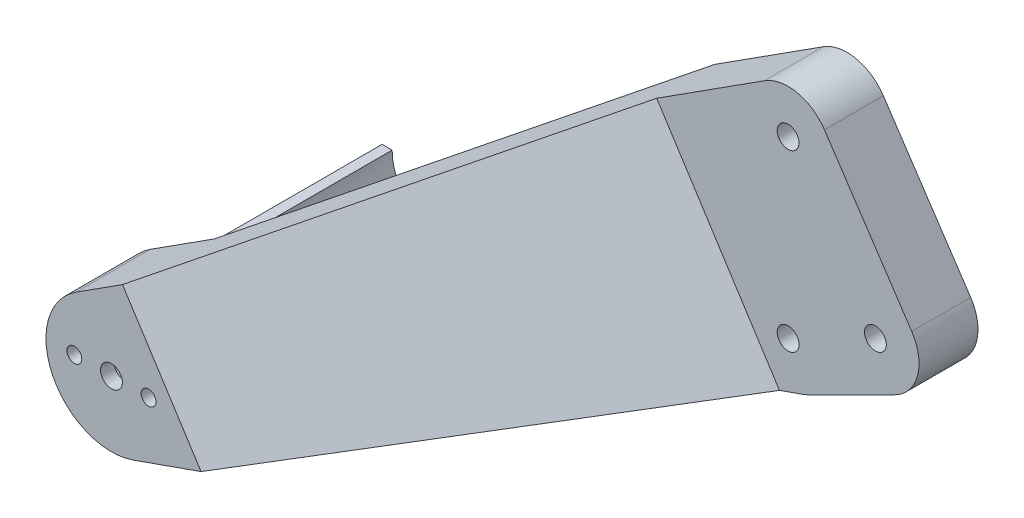
SolidWorks part; units mm, degrees
ref_plane "Front Plane" through (0, 0, 0) normal (0, 0, 1) x (1, 0, 0)
ref_plane "Top Plane" through (0, 0, 0) normal (0, 1, 0) x (1, 0, 0)
ref_plane "Right Plane" through (0, 0, 0) normal (1, 0, 0) x (0, 0, -1)
sketch "Sketch1" plane through (0, 0, 0) normal (0, 0, 1) x (1, 0, 0)
  line L1 (3.3289, -9.4297) -> (-95.0067, -44.1445)
  line L2 (-108.0914, -17.3695) -> (-5.3942, 48.4203)
  line L3 (8.3205, 45.547) -> (28.3205, 15.547)
  line L4 (24.4721, 1.0557) -> (4.4721, -8.9443)
  arc A0 (4.4721, -8.9443) -> (3.3289, -9.4297) centre (0, 0) cw
  arc A1 (-95.0067, -44.1445) -> (-108.0914, -17.3695) centre (-100, -30) cw
  arc A2 (-5.3942, 48.4203) -> (8.3205, 45.547) centre (0, 40) cw
  arc A3 (28.3205, 15.547) -> (24.4721, 1.0557) centre (20, 10) cw
  dimension "D1" = 15
  dimension "D5" = 10
  dimension "D8" = 10
  dimension "D9" = 10
  dimension "D2" = 30
  dimension "D3" = 40
  dimension "D4" = 100
  dimension "D6" = 20
  dimension "D7" = 30
extrude "Boss-Extrude1" add sketch "Sketch1" along normal blind 17
sketch "Sketch2" plane through (0, 0, 17) normal (0, 0, 1) x (1, 0, 0)
  circle A0 centre (-100, -30) radius 2.5
  circle A1 centre (0, 0) radius 2.5
  circle A2 centre (0, 40) radius 2.5
  circle A3 centre (20, 10) radius 2.5
  arc A4 (24.4721, 1.0557) -> (28.3205, 15.547) centre (20, 10) ccw construction
  dimension "D1" = 5
  dimension "D2" = 5
extrude "Cut-Extrude1" cut sketch "Sketch2" against normal through all
sketch "Sketch3" plane through (0, 0, 17) normal (0, 0, 1) x (1, 0, 0)
  line L0 (-108.5, -30) -> (-91.5, -30) construction
  circle A0 centre (-108.5, -30) radius 1.7
  circle A1 centre (-91.5, -30) radius 1.7
  circle A3 centre (-100, -30) radius 2.5 construction
  point P4 (-100, -30)
  dimension "D1" = 3.4
  dimension "D2" = 17
extrude "Cut-Extrude2" cut sketch "Sketch3" against normal through all
sketch "Sketch7" plane through (0, 0, 0) normal (0, 0, -1) x (-1, 0, 0)
  circle A0 centre (100, -30) radius 12.7
  dimension "D1" = 25.4
extrude "Cut-Extrude6" cut sketch "Sketch7" against normal blind 13
sketch "Sketch6" plane through (0, 0, 17) normal (0, 0, 1) x (1, 0, 0)
  circle A0 centre (-100, -30) radius 12.7
  dimension "D1" = 25.4
extrude "Cut-Extrude5" [suppressed] cut sketch "Sketch6" against normal blind 13
sketch "Sketch4" [suppressed] plane through (0, 0, 13) normal (0, 0, -1) x (-1, 0, 0)
  circle A0 centre (100, -30) radius 5.5
  dimension "D1" = 11
extrude "Cut-Extrude3" cut sketch "Sketch4" against normal blind 0.9
sketch "Sketch5" [suppressed] plane through (0, 0, 4) normal (0, 0, 1) x (1, 0, 0)
  circle A0 centre (-100, -30) radius 5.5
  dimension "D1" = 11
extrude "Cut-Extrude4" [suppressed] cut sketch "Sketch5" against normal blind 0.9
sketch "Sketch8" plane through (0, 0, 0) normal (0, 0, -1) x (-1, 0, 0)
  line L0 (112.7, -30) -> (115, -30)
  line L2 (87.0096, -37.5) -> (89.0015, -36.35)
  line L4 (-8.3205, 45.547) -> (-28.3205, 15.547)
  line L5 (-24.4721, 1.0557) -> (-4.4721, -8.9443)
  line L6 (-3.3289, -9.4297) -> (95.0067, -44.1445)
  line L7 (108.0914, -17.3695) -> (5.3942, 48.4203)
  circle A0 centre (100, -30) radius 12.7 construction
  circle A1 centre (100, -30) radius 12.7 construction
  arc A2 (89.0015, -36.35) -> (112.7, -30) centre (100, -30) ccw
  arc A4 (5.3942, 48.4203) -> (-8.3205, 45.547) centre (0, 40) ccw
  arc A5 (-28.3205, 15.547) -> (-24.4721, 1.0557) centre (-20, 10) ccw
  arc A6 (-4.4721, -8.9443) -> (-3.3289, -9.4297) centre (0, 0) ccw
  arc A7 (95.0067, -44.1445) -> (108.0914, -17.3695) centre (100, -30) ccw
  arc A11 (87.0096, -37.5) -> (115, -30) centre (100, -30) ccw
  dimension "D2" = 150
  dimension "D1" = 0
extrude "Boss-Extrude2" add sketch "Sketch8" along normal blind 60
sketch "Sketch9" [suppressed] plane through (0, 0, 17) normal (0, 0, 1) x (1, 0, 0)
  line L0 (-90.2712, -38.1634) -> (-88.5093, -39.6418)
  line L1 (-112.7, -30) -> (-115, -30)
  circle A0 centre (-100, -30) radius 12.7 construction
  arc A1 (-112.7, -30) -> (-90.2712, -38.1634) centre (-100, -30) ccw
  arc A3 (-115, -30) -> (-88.5093, -39.6418) centre (-100, -30) ccw
  dimension "D1" = 15
  dimension "D2" = 140
extrude "Boss-Extrude3" [suppressed] add sketch "Sketch9" along normal blind 60
sketch "Sketch10" plane through (0, 0, 0) normal (0, 0, -1) x (-1, 0, 0)
  line L0 (-3.3289, -9.4297) -> (74.8434, -37.0264)
  line L1 (95.0067, -44.1445) -> (-3.3289, -9.4297) construction
  line L2 (74.8434, -37.0264) -> (93.4462, -7.9875)
  line L6 (112.7, -30) -> (115, -30)
  line L7 (108.0914, -17.3695) -> (5.3942, 48.4203)
  line L8 (-8.3205, 45.547) -> (-28.3205, 15.547)
  line L9 (-24.4721, 1.0557) -> (-4.4721, -8.9443)
  line L10 (-3.3289, -9.4297) -> (95.0067, -44.1445)
  line L11 (87.0096, -37.5) -> (89.0015, -36.35)
  line L19 (93.4462, -7.9875) -> (5.3942, 48.4203)
  line L20 (-8.3205, 45.547) -> (-28.3205, 15.547)
  line L21 (-24.4721, 1.0557) -> (-4.4721, -8.9443)
  arc A6 (115, -30) -> (108.0914, -17.3695) centre (100, -30) ccw
  arc A7 (5.3942, 48.4203) -> (-8.3205, 45.547) centre (0, 40) ccw
  arc A8 (-28.3205, 15.547) -> (-24.4721, 1.0557) centre (-20, 10) ccw
  arc A10 (-4.4721, -8.9443) -> (-3.3289, -9.4297) centre (0, 0) ccw
  arc A11 (87.0096, -37.5) -> (95.0067, -44.1445) centre (100, -30) ccw
  arc A18 (112.7, -30) -> (89.0015, -36.35) centre (100, -30) ccw
  arc A20 (5.3942, 48.4203) -> (-8.3205, 45.547) centre (0, 40) ccw
  arc A21 (-28.3205, 15.547) -> (-24.4721, 1.0557) centre (-20, 10) ccw
  arc A22 (-4.4721, -8.9443) -> (-3.3289, -9.4297) centre (0, 0) ccw
  dimension "D2" = 115
  dimension "D1" = 0
extrude "Boss-Extrude4" add sketch "Sketch10" along normal blind 51.5
sketch "Sketch12" plane through (0, 0, 17) normal (0, 0, 1) x (1, 0, 0)
  circle A0 centre (0, 0) radius 2.5 construction
  circle A1 centre (20, 10) radius 2.5 construction
  circle A2 centre (0, 40) radius 2.5 construction
  circle A3 centre (0, 0) radius 2.5
  circle A4 centre (20, 10) radius 2.5
  circle A5 centre (0, 40) radius 2.5
extrude "Cut-Extrude7" cut sketch "Sketch12" against normal through all
sketch "Sketch13" plane through (-23.5628, 36.7812, 0) normal (-0.5394, 0.842, 0) x (0.842, 0.5394, 0)
  line L0 (32.2333, -17) -> (-87.7667, -17)
  line L1 (21.577, -17) -> (-100.3861, -17) construction
  line L2 (-87.7667, -17) -> (-7.7667, 38)
  line L3 (-7.7667, 38) -> (32.2333, 38)
  line L4 (32.2333, -17) -> (32.2333, 51.5) construction
  line L7 (32.2333, 38) -> (33.2333, 38)
  line L9 (32.2333, -17) -> (33.2333, -17)
  line L10 (33.2333, 38) -> (33.2333, -17)
  dimension "D1" = 55
  dimension "D2" = 120
  dimension "D3" = 40
  dimension "D4" = 1
extrude "Cut-Extrude8" cut sketch "Sketch13" against normal through all
sketch "Sketch14" plane through (-23.5628, 36.7812, 0) normal (-0.5394, 0.842, 0) x (0.842, 0.5394, 0)
  line L0 (-82.9936, 0) -> (-7.9936, 51.5)
  line L1 (-82.9936, 51.5) -> (21.577, 51.5) construction
  line L2 (-7.9936, 51.5) -> (-82.9936, 51.5)
  line L3 (-82.9936, 51.5) -> (-82.9936, 0)
  dimension "D1" = 75
extrude "Cut-Extrude9" cut sketch "Sketch14" against normal through all
sketch "Sketch15" [suppressed] plane through (0, 0, 17) normal (0, 0, 1) x (1, 0, 0)
  line L0 (-93.4462, -7.9875) -> (-74.8434, -37.0264)
  line L6 (-90.2712, -38.1634) -> (-88.5093, -39.6418)
  line L7 (-95.0067, -44.1445) -> (3.3289, -9.4297)
  line L8 (4.4721, -8.9443) -> (24.4721, 1.0557)
  line L9 (28.3205, 15.547) -> (8.3205, 45.547)
  line L10 (-5.3942, 48.4203) -> (-108.0914, -17.3695)
  line L11 (-115, -30) -> (-112.7, -30)
  line L13 (-74.8434, -37.0264) -> (3.3289, -9.4297)
  line L14 (4.4721, -8.9443) -> (24.4721, 1.0557)
  line L15 (28.3205, 15.547) -> (8.3205, 45.547)
  line L16 (-5.3942, 48.4203) -> (-93.4462, -7.9875)
  arc A6 (-95.0067, -44.1445) -> (-88.5093, -39.6418) centre (-100, -30) ccw
  arc A7 (3.3289, -9.4297) -> (4.4721, -8.9443) centre (0, 0) ccw
  arc A8 (24.4721, 1.0557) -> (28.3205, 15.547) centre (20, 10) ccw
  arc A9 (8.3205, 45.547) -> (-5.3942, 48.4203) centre (0, 40) ccw
  arc A10 (-108.0914, -17.3695) -> (-115, -30) centre (-100, -30) ccw
  arc A11 (-90.2712, -38.1634) -> (-112.7, -30) centre (-100, -30) ccw
  arc A13 (3.3289, -9.4297) -> (4.4721, -8.9443) centre (0, 0) ccw
  arc A14 (24.4721, 1.0557) -> (28.3205, 15.547) centre (20, 10) ccw
  arc A15 (8.3205, 45.547) -> (-5.3942, 48.4203) centre (0, 40) ccw
  dimension "D2" = 115
  dimension "D1" = 0
extrude "Boss-Extrude5" [suppressed] add sketch "Sketch15" along normal blind 51.5
sketch "Sketch16" [suppressed] plane through (0, 0, 0) normal (0, 0, -1) x (-1, 0, 0)
  circle A0 centre (0, 0) radius 2.5 construction
  circle A1 centre (-20, 10) radius 2.5 construction
  circle A2 centre (0, 40) radius 2.5 construction
  circle A3 centre (0, 0) radius 2.5
  circle A4 centre (-20, 10) radius 2.5
  circle A5 centre (0, 40) radius 2.5
extrude "Cut-Extrude10" [suppressed] cut sketch "Sketch16" against normal through all
sketch "Sketch17" [suppressed] plane through (-23.5628, 36.7812, 0) normal (-0.5394, 0.842, 0) x (0.842, 0.5394, 0)
  line L0 (32.2333, 0) -> (-87.7667, 0)
  line L1 (21.577, 0) -> (-100.3861, 0) construction
  line L2 (-87.7667, 0) -> (-7.7667, -55)
  line L3 (-7.7667, -55) -> (32.2333, -55)
  line L4 (32.2333, -68.5) -> (32.2333, 0) construction
  line L7 (32.2333, -55) -> (33.2333, -55)
  line L9 (32.2333, 0) -> (33.2333, 0)
  line L10 (33.2333, -55) -> (33.2333, 0)
  dimension "D1" = 120
  dimension "D2" = 40
  dimension "D3" = 55
  dimension "D4" = 1
extrude "Cut-Extrude11" [suppressed] cut sketch "Sketch17" against normal through all
sketch "Sketch18" [suppressed] plane through (-23.5628, 36.7812, 0) normal (-0.5394, 0.842, 0) x (0.842, 0.5394, 0)
  line L0 (-82.9936, -17) -> (-82.9936, -68.5)
  line L1 (-82.9936, -68.5) -> (-7.9936, -68.5)
  line L3 (-7.9936, -68.5) -> (-82.9936, -17)
  dimension "D1" = 75
extrude "Cut-Extrude12" [suppressed] cut sketch "Sketch18" against normal through all
